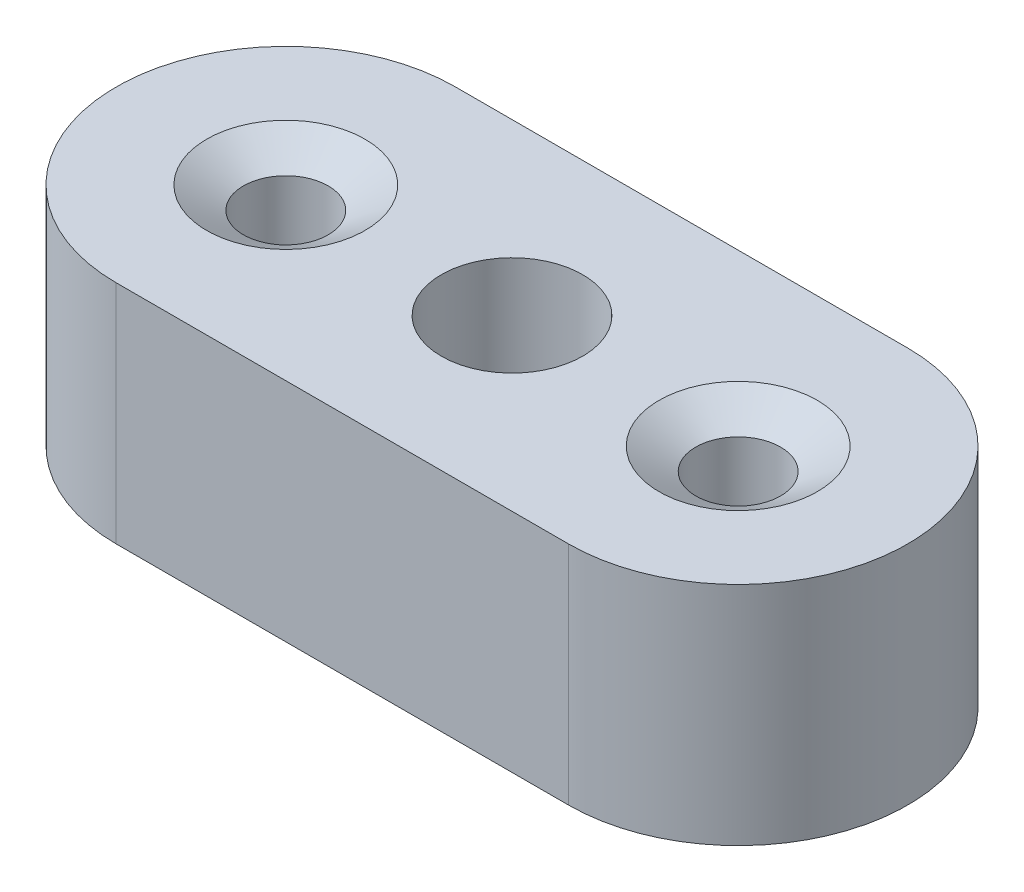
SolidWorks part; units mm, degrees
ref_plane "Front Plane" through (0, 0, 0) normal (0, 0, 1) x (1, 0, 0)
ref_plane "Top Plane" through (0, 0, 0) normal (0, 1, 0) x (1, 0, 0)
ref_plane "Right Plane" through (0, 0, 0) normal (1, 0, 0) x (0, 0, -1)
sketch "Sketch1" plane through (0, 0, 0) normal (0, 1, 0) x (1, 0, 0)
  line L0 (-12.7, 0) -> (12.7, 0) construction
  line L1 (-12.7, 9.525) -> (12.7, 9.525)
  line L2 (-12.7, -9.525) -> (12.7, -9.525)
  arc A0 (-12.7, 9.525) -> (-12.7, -9.525) centre (-12.7, 0) ccw
  arc A1 (12.7, -9.525) -> (12.7, 9.525) centre (12.7, 0) ccw
  circle A2 centre (0, 0) radius 3.9688
  point P2 (0, 0)
  dimension "D1" = 7.9375
  dimension "D2" = 25.4
  dimension "D3" = 19.05
extrude "Boss-Extrude1" add sketch "Sketch1" along normal blind 12.7
ref_axis "Axis1" through (-12.7, 12.7, 0) along (0, -1, 0)
sketch "Sketch2" plane through (0, 0, 0) normal (0, 0, 1) x (1, 0, 0)
  line L0 (-12.7, 12.7) -> (-17.145, 12.7)
  line L1 (-17.145, 12.7) -> (-15.0812, 11.46)
  line L2 (-15.0812, 11.46) -> (-15.0812, 0)
  line L3 (-15.0812, 0) -> (-12.7, 0)
  line L4 (-12.7, 0) -> (-12.7, 12.7) construction
  line L5 (-12.7, 12.7) -> (-12.7, 0) construction
  line L8 (-22.225, 0) -> (-12.7, 0) construction
  line L9 (-12.7, 12.7) -> (-22.225, 12.7) construction
  line L10 (-12.7, 12.7) -> (-12.7, 0)
  dimension "D1" = 4.7625
  dimension "D2" = 59
  dimension "D3" = 8.89
revolve "Cut-Revolve1" cut sketch "Sketch2" angle 360 about L4
mirror "Mirror1" about plane through (0, 0, 0) normal (1, 0, 0) of "Cut-Revolve1"
